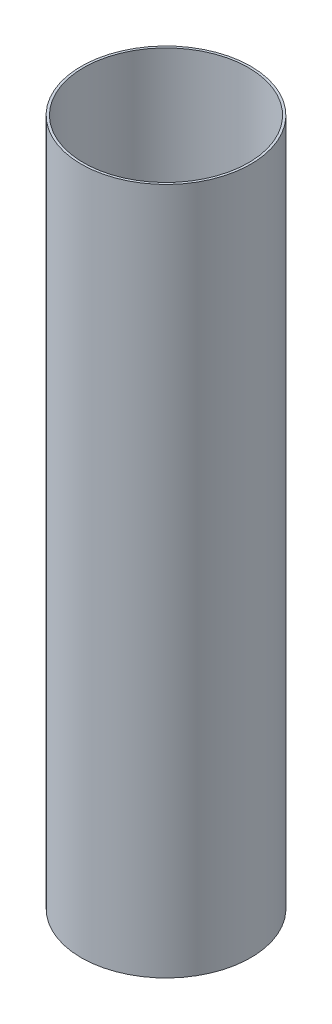
SolidWorks part; units mm, degrees
material "C-Glass Fiber"
ref_plane "Front Plane" through (0, 0, 0) normal (0, 0, 1) x (1, 0, 0)
ref_plane "Top Plane" through (0, 0, 0) normal (0, 1, 0) x (1, 0, 0)
ref_plane "Right Plane" through (0, 0, 0) normal (1, 0, 0) x (0, 0, -1)
sketch "Sketch2" plane through (0, 0, 0) normal (0, 1, 0) x (1, 0, 0)
  circle A0 centre (0, 0) radius 78.359
  circle A1 centre (0, 0) radius 76.2
  dimension "D1" = 152.4
  dimension "D2" = 156.718
extrude "Boss-Extrude1" add sketch "Sketch2" along normal blind 635
equation "\"Outer Diameter\"= 6.17"
equation "\"Inner Diameter\"= 6"
equation "\"Length\"= 25"
equation "\"D1@Sketch2\"=\"Inner Diameter\""
equation "\"D2@Sketch2\"=\"Outer Diameter\""
equation "\"D1@Boss-Extrude1\"=\"Length\""
